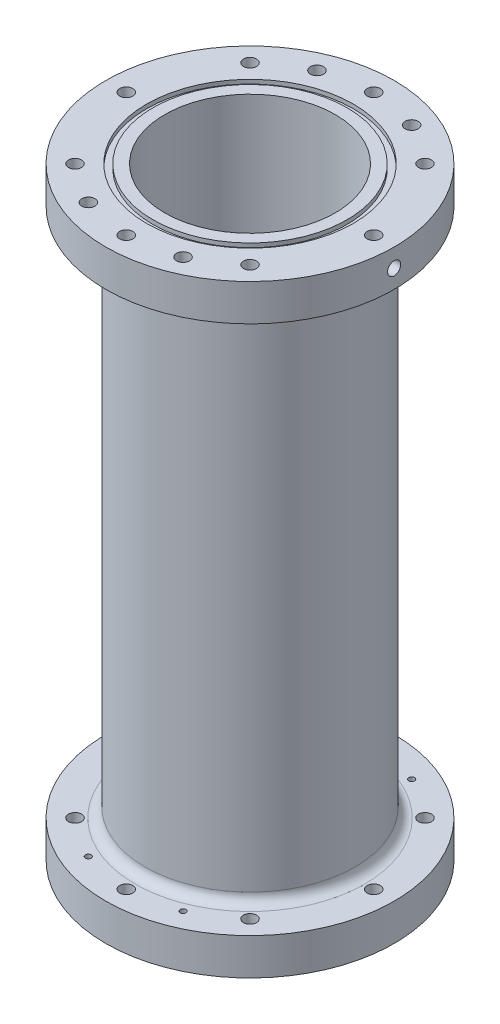
SolidWorks part; units mm, degrees
ref_plane "Front Plane" through (0, 0, 0) normal (0, 0, 1) x (1, 0, 0)
ref_plane "Top Plane" through (0, 0, 0) normal (0, 1, 0) x (1, 0, 0)
ref_plane "Right Plane" through (0, 0, 0) normal (1, 0, 0) x (0, 0, -1)
sketch "Sketch2" plane through (0, 0, 0) normal (0, 1, 0) x (1, 0, 0)
  circle A0 centre (0, 0) radius 41.275
  circle A1 centre (0, 0) radius 50.8
  dimension "D1" = 101.6
  dimension "D2" = 82.55
extrude "Base Cylinder" add sketch "Sketch2" along normal blind 292.1
sketch "Sketch3" plane through (0, 0, 0) normal (0, -1, 0) x (1, 0, 0)
  circle A0 centre (0, 0) radius 41.275
  circle A1 centre (0, 0) radius 69.85
  dimension "D1" = 139.7
extrude "Aft Flange" add sketch "Sketch3" against normal blind 17.78
sketch "Sketch4" plane through (0, 292.1, 0) normal (0, 1, 0) x (1, 0, 0)
  circle A0 centre (0, 0) radius 41.275
  circle A1 centre (0, 0) radius 69.85
extrude "Forward Flange" add sketch "Sketch4" against normal blind 17.78
sketch "Sketch6" plane through (0, 0, 0) normal (0, -1, 0) x (1, 0, 0)
  circle A0 centre (0, 0) radius 50.0761
  circle A1 centre (0, 0) radius 47.0027
  dimension "D1" = 100.1522
  dimension "D2" = 94.0054
extrude "O-Ring Slot 1" cut sketch "Sketch6" against normal blind 1.9812
sketch "Sketch7" plane through (0, 292.1, 0) normal (0, 1, 0) x (1, 0, 0)
  circle A0 centre (0, 0) radius 50.0761
  circle A1 centre (0, 0) radius 47.0027
  dimension "D1" = 100.1522
  dimension "D2" = 94.0054
extrude "O-Ring Slot 2" cut sketch "Sketch7" against normal blind 1.9812
sketch "Sketch8" plane through (0, 0, 0) normal (0, -1, 0) x (1, 0, 0)
  circle A0 centre (-59.9186, 0) radius 3.175
  circle A1 centre (-42.3688, 42.3688) radius 3.175
  circle A2 centre (0, 59.9186) radius 3.175
  circle A3 centre (42.3688, 42.3688) radius 3.175
  circle A4 centre (59.9186, 0) radius 3.175
  circle A5 centre (42.3688, -42.3688) radius 3.175
  circle A6 centre (0, -59.9186) radius 3.175
  circle A7 centre (-42.3688, -42.3688) radius 3.175
  point P36 (0, 0)
  dimension "D2" = 6.35
  dimension "D1" = 59.9186
  dimension "D3" = 8
extrude "Cut-Extrude4" cut sketch "Sketch8" against normal through all both and the other way through all
fillet "Fillet1" radius 4.7625 2 edges at (0, 17.78, -50.8) (0, 274.32, 50.8)
sketch "Sketch9" plane through (0, 292.1, 0) normal (0, 1, 0) x (1, 0, 0)
  line L0 (0, -76.2) -> (0, 76.2) construction
  line L1 (-32.6024, 78.7092) -> (32.6024, -78.7092) construction
  line L2 (-32.0538, -77.3847) -> (32.0538, 77.3847) construction
  circle A0 centre (0, 0) radius 59.9186 construction
  circle A1 centre (-22.9299, 55.3576) radius 3.175
  circle A2 centre (22.9299, -55.3576) radius 3.175
  circle A3 centre (22.9299, 55.3576) radius 3.175
  circle A4 centre (-22.9299, -55.3576) radius 3.175
  point P6 (0, 0)
  point P9 (0, 0)
  point P16 (0, 0)
  dimension "D1" = 119.8372
  dimension "D3" = 6.35
  dimension "D4" = 6.35
  dimension "D5" = 6.35
  dimension "D6" = 6.35
  dimension "D2" = 22.5
  dimension "D7" = 22.5
extrude "Cut-Extrude5" cut sketch "Sketch9" against normal blind 7.62
sketch "Sketch10" plane through (0, 0, 0) normal (0, -1, 0) x (1, 0, 0)
  line L0 (0, -76.2) -> (0, 76.2) construction
  line L1 (-33.7592, 81.5019) -> (33.7592, -81.5019) construction
  line L2 (-33.8465, -81.7128) -> (33.8465, 81.7128) construction
  circle A0 centre (0, 0) radius 59.9186 construction
  circle A1 centre (-22.9299, 55.3576) radius 3.175
  circle A2 centre (22.9299, -55.3576) radius 3.175
  circle A3 centre (22.9299, 55.3576) radius 3.175
  circle A4 centre (-22.9299, -55.3576) radius 3.175
  point P6 (0, 0)
  point P9 (0, 0)
  point P16 (0, 0)
  dimension "D1" = 119.8372
  dimension "D2" = 6.35
  dimension "D3" = 6.35
  dimension "D5" = 6.35
  dimension "D6" = 6.35
  dimension "D4" = 22.5
  dimension "D7" = 22.5
extrude "Cut-Extrude6" cut sketch "Sketch10" against normal blind 7.62
sketch "Sketch11" plane through (0, 284.48, 0) normal (0, 1, 0) x (1, 0, 0)
  circle A0 centre (-22.9299, 55.3576) radius 1.4097
  circle A1 centre (22.9299, 55.3576) radius 1.4097
  circle A2 centre (-22.9299, -55.3576) radius 1.4097
  circle A3 centre (22.9299, -55.3576) radius 1.4097
  dimension "D1" = 2.8194
  dimension "D2" = 2.8194
  dimension "D3" = 2.8194
  dimension "D4" = 2.8194
extrude "Cut-Extrude7" cut sketch "Sketch11" against normal up to next
sketch "Sketch12" plane through (0, 7.62, 0) normal (0, -1, 0) x (1, 0, 0)
  circle A0 centre (-22.9299, 55.3576) radius 1.4097
  circle A1 centre (22.9299, 55.3576) radius 1.4097
  circle A2 centre (-22.9299, -55.3576) radius 1.4097
  circle A3 centre (22.9299, -55.3576) radius 1.4097
  dimension "D1" = 2.8194
  dimension "D2" = 2.8194
  dimension "D3" = 2.8194
  dimension "D4" = 2.8194
extrude "Cut-Extrude8" cut sketch "Sketch12" against normal up to next
ref_plane "Plane1" through (-69.85, 0, 0) normal (1, 0, 0) x (0, 0, -1)
ref_plane "Plane3" through (69.85, 0, 0) normal (1, 0, 0) x (0, 0, -1)
ref_plane "Plane4" through (0, 283.21, 0) normal (0, 1, 0) x (1, 0, 0)
sketch "Sketch13" plane through (-69.85, 0, 0) normal (1, 0, 0) x (0, 0, -1)
  line L0 (76.835, 283.21) -> (-76.835, 283.21) construction
  circle A0 centre (0, 283.21) radius 3.175
  dimension "D1" = 6.35
extrude "Cut-Extrude10" cut sketch "Sketch13" along normal blind 6.35
sketch "Sketch14" plane through (69.85, 0, 0) normal (1, 0, 0) x (0, 0, -1)
  circle A0 centre (0, 283.21) radius 3.175
  dimension "D1" = 6.35
extrude "Cut-Extrude11" cut sketch "Sketch14" against normal blind 6.35
ref_axis "Axis1" through (63.5, 283.21, 0) along (1, 0, 0)
ref_axis "Axis2" through (-63.5, 283.21, 0) along (-1, 0, 0)
